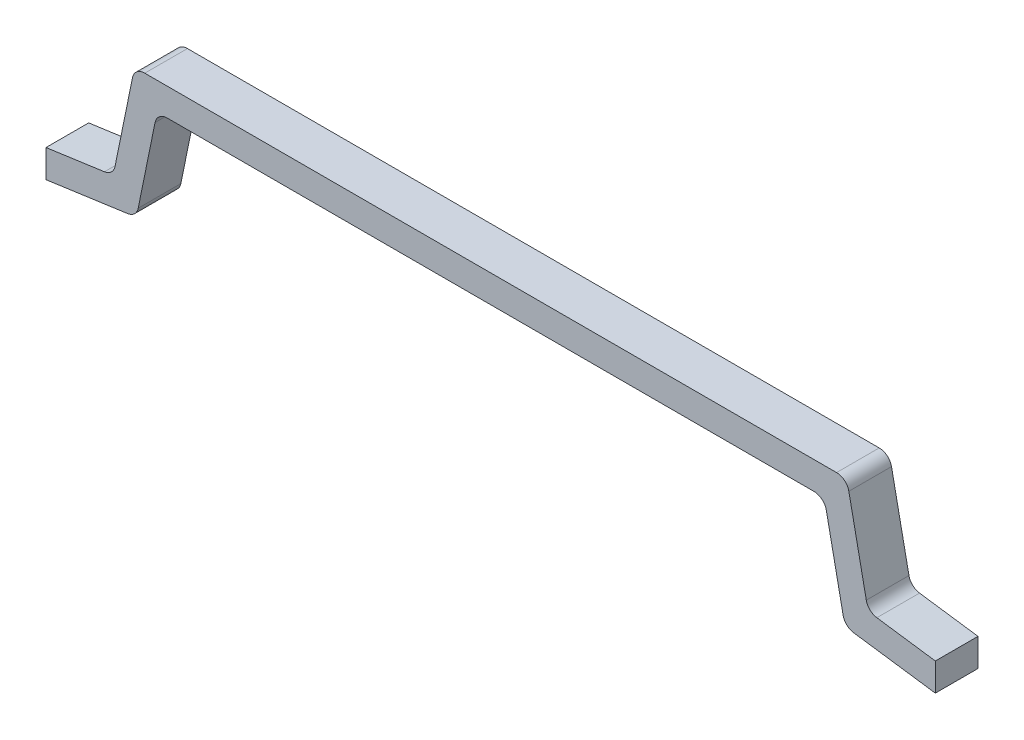
SolidWorks part; units mm, degrees
ref_plane "Front Plane" through (0, 0, 0) normal (0, 0, 1) x (1, 0, 0)
ref_plane "Top Plane" through (0, 0, 0) normal (0, 1, 0) x (1, 0, 0)
ref_plane "Right Plane" through (0, 0, 0) normal (1, 0, 0) x (0, 0, -1)
sketch "Sketch2" plane through (0, 0, 0) normal (0, 0, 1) x (1, 0, 0)
  line L0 (0, 0) -> (0, 0.2801)
  line L1 (1.0582, 1.64) -> (1.515, 1.64)
  line L2 (1.515, 1.64) -> (1.515, 1.31)
  line L3 (0, 0.2801) -> (0, -0.0768) construction
  line L4 (1.27, 2.5114) -> (1.27, 1.64) construction
  line L5 (0.804, 0.3931) -> (1.0582, 1.64)
  line L6 (-0.3355, 0.2801) -> (0, 0.2801) construction
  line L7 (1.1481, 0.4292) -> (1.1481, 0.4292)
  line L8 (1.1481, 0.4292) -> (1.1481, 0.4292)
  line L9 (0.804, 0.3931) -> (0, 0.2801)
  line L10 (1.1481, 0.4292) -> (1.0807, 0.0988)
  line L11 (-0.2646, -0.0531) -> (1.6458, -0.0531) construction
  line L12 (1.0807, 0.0988) -> (0, -0.0531)
  line L13 (0, 0.2801) -> (0, -0.0531)
  line L15 (1.27, 1.64) -> (1.1046, 0.1021) construction
  line L16 (0.9419, 1.6753) -> (0.804, 0.3931) construction
  line L17 (1.1481, 0.4292) -> (1.1481, 0.4292)
  line L18 (1.1481, 0.4292) -> (1.1481, 0.4292)
  line L19 (1.1481, 0.4292) -> (1.3277, 1.31)
  line L21 (1.1046, 0.1021) -> (0.0459, -0.0467) construction
  line L22 (1.3277, 1.31) -> (1.515, 1.31)
  line L23 (1.1481, 0.4292) -> (1.3816, 1.5741) construction
  line L24 (0, -0.0768) -> (0.0459, -0.0467) construction
  dimension "D1" = 1.515
  dimension "D5" = 0.33
  dimension "D6" = 8
  dimension "D7" = 0.33
  dimension "D8" = 0.33
extrude "Boss-Extrude1" add sketch "Sketch2" along normal blind 0.51 contours L19 L22 L2 L1 L5 L9 L0 L13 L12 region at (0.8794, 0.6829, 0)
fillet "Fillet2" radius 0.15 4 edges at (1.0582, 1.64, 0.255) (1.3277, 1.31, 0.255) (1.0807, 0.0988, 0.255) (0.804, 0.3931, 0.255)
sketch "Sketch3" plane through (1.515, 0, 0) normal (1, 0, 0) x (0, 0, -1)
  line L4 (0, 1.31) -> (0, 1.64)
  line L5 (0, 1.64) -> (-0.51, 1.64)
  line L6 (-0.51, 1.64) -> (-0.51, 1.31)
  line L7 (-0.51, 1.31) -> (0, 1.31)
  line L8 (0, 1.31) -> (0, 1.64)
  line L9 (0, 1.64) -> (-0.51, 1.64)
  line L10 (-0.51, 1.64) -> (-0.51, 1.31)
  line L11 (-0.51, 1.31) -> (0, 1.31)
  dimension "D1" = 0
extrude "Boss-Extrude2" add sketch "Sketch3" along normal blind 3.8
mirror "Mirror2" about plane through (5.315, 0, 0) normal (1, 0, 0) of "Boss-Extrude2", "Fillet2", "Boss-Extrude1"
